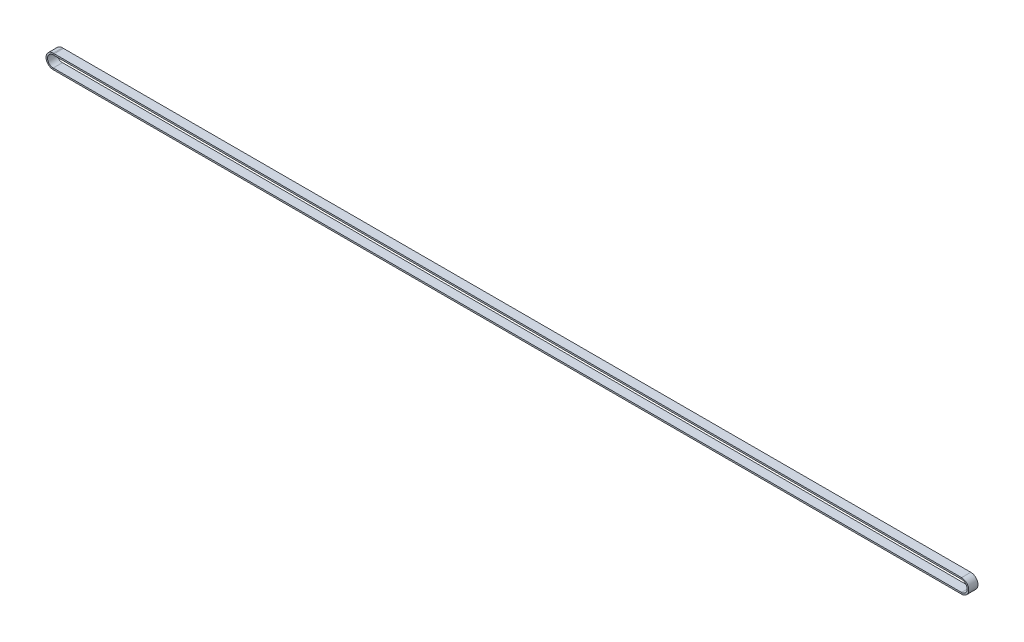
SolidWorks part; units mm, degrees
ref_plane "Front Plane" through (0, 0, 0) normal (0, 0, 1) x (1, 0, 0)
ref_plane "Top Plane" through (0, 0, 0) normal (0, 1, 0) x (1, 0, 0)
ref_plane "Right Plane" through (0, 0, 0) normal (1, 0, 0) x (0, 0, -1)
sketch "Sketch2" plane through (0, 0, 0) normal (0, 0, 1) x (1, 0, 0)
  line L0 (0, 0) -> (1, 0) construction
  line L1 (0, 0) -> (0, 1) construction
  line L2 (-1, -84.243) -> (883.5204, -84.243)
  line L3 (883.5204, -98.243) -> (-1, -98.243)
  arc A0 (-1, -98.243) -> (-1, -84.243) centre (-1, -91.243) cw
  arc A1 (883.5204, -84.243) -> (883.5204, -98.243) centre (883.5204, -91.243) cw
sketch "Sketch3" plane through (0, 0, 0) normal (1, 0, 0) x (0, 0, -1)
  line L1 (0, -85.743) -> (-9, -85.743)
  line L2 (0, -85.743) -> (0, -84.243)
  line L3 (0, -84.243) -> (-9, -84.243)
  line L4 (-9, -85.743) -> (-9, -84.243)
  dimension "D1" = 9
  dimension "D2" = 1.5
sweep "Sweep1" add profiles "Sketch3" path "Sketch2"
